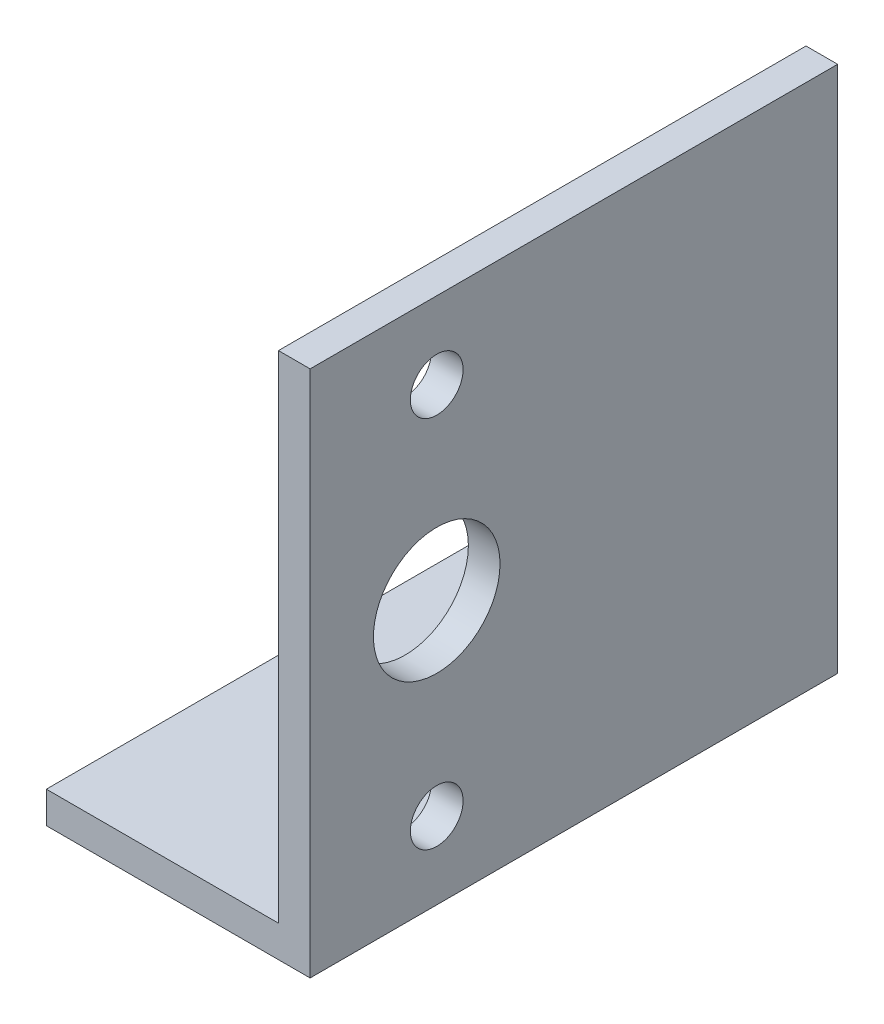
SolidWorks part; units mm, degrees
ref_plane "Alzado" through (0, 0, 0) normal (0, 0, 1) x (1, 0, 0)
ref_plane "Planta" through (0, 0, 0) normal (0, 1, 0) x (1, 0, 0)
ref_plane "Vista lateral" through (0, 0, 0) normal (1, 0, 0) x (0, 0, -1)
sketch "Croquis1" plane through (0, 0, 0) normal (0, 0, 1) x (1, 0, 0)
  line L0 (-25, 0) -> (0, 0)
  line L1 (0, 0) -> (0, 50)
  line L2 (-25, 3) -> (-3, 3)
  line L3 (-3, 3) -> (-3, 50)
  line L4 (-25, 3) -> (-25, 0)
  line L5 (-3, 50) -> (0, 50)
  dimension "D1" = 50
  dimension "D2" = 25
  dimension "D3" = 3
extrude "Saliente-Extruir1" add sketch "Croquis1" along normal blind 50
sketch "Croquis2" plane through (0, 0, 0) normal (1, 0, 0) x (0, 0, -1)
  line L0 (-38, 50) -> (-38, 0) construction
  line L1 (-50, 50) -> (0, 50) construction
  line L2 (-50, 0) -> (0, 0) construction
  line L3 (-50, 0) -> (-50, 50) construction
  line L4 (-50, 25) -> (0, 25) construction
  line L5 (0, 0) -> (0, 50) construction
  circle A0 centre (-38, 25) radius 6
  circle A1 centre (-38, 42.7) radius 2.5
  circle A2 centre (-38, 7.3) radius 2.5
  dimension "D3" = 12
  dimension "D6" = 5
  dimension "D1" = 12
  dimension "D2" = 25
  dimension "D4" = 35.4
  dimension "D5" = 17.7
extrude "Cortar-Extruir1" cut sketch "Croquis2" against normal up to surface (3 mm away) up to face at (-3, 26.5, 25)
equation "\"D5@Croquis2\"=\"D4@Croquis2\"/2"
